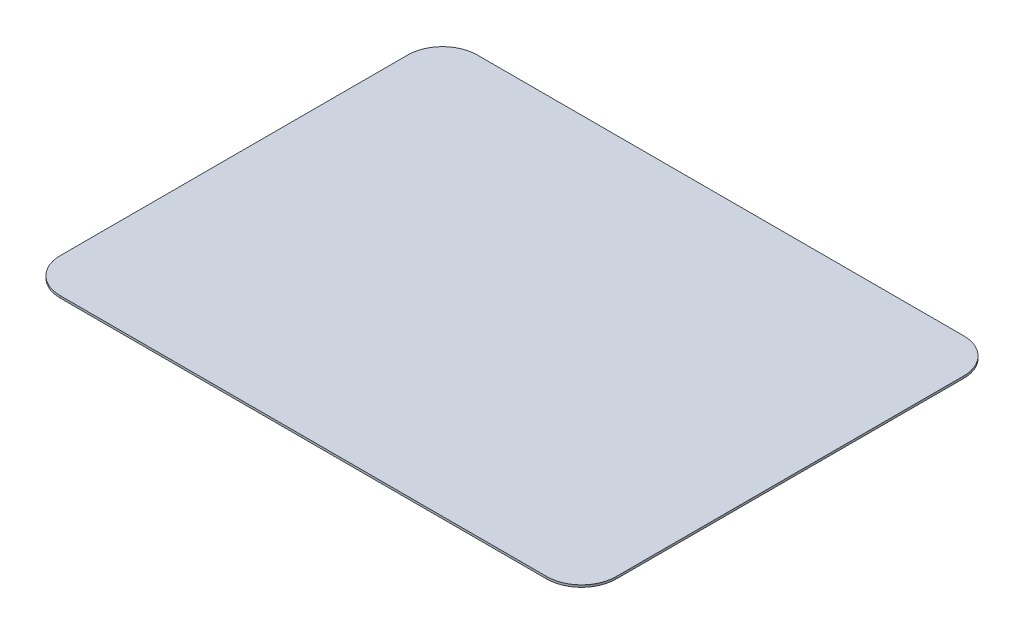
SolidWorks part; units mm, degrees
ref_plane "Front Plane" through (0, 0, 0) normal (0, 0, 1) x (1, 0, 0)
ref_plane "Top Plane" through (0, 0, 0) normal (0, 1, 0) x (1, 0, 0)
ref_plane "Right Plane" through (0, 0, 0) normal (1, 0, 0) x (0, 0, -1)
ref_plane "SheetPlane" through (0, 6.731, 0) normal (0, 1, 0) x (1, 0, 0)
sketch "Sketch1" plane through (0, 6.731, 0) normal (0, 1, 0) x (1, 0, 0)
  line L4 (101.6, -63.5) -> (101.6, 63.5)
  line L5 (88.9, 76.2) -> (-88.9, 76.2)
  line L6 (-101.6, 63.5) -> (-101.6, -63.5)
  line L7 (-88.9, -76.2) -> (88.9, -76.2)
  line L8 (101.6, -63.5) -> (101.6, 63.5)
  line L9 (88.9, 76.2) -> (-88.9, 76.2)
  line L10 (-101.6, 63.5) -> (-101.6, -63.5)
  line L11 (-88.9, -76.2) -> (88.9, -76.2)
  arc A4 (88.9, -76.2) -> (101.6, -63.5) centre (88.9, -63.5) ccw
  arc A5 (101.6, 63.5) -> (88.9, 76.2) centre (88.9, 63.5) ccw
  arc A6 (-88.9, 76.2) -> (-101.6, 63.5) centre (-88.9, 63.5) ccw
  arc A7 (-101.6, -63.5) -> (-88.9, -76.2) centre (-88.9, -63.5) ccw
  arc A8 (88.9, -76.2) -> (101.6, -63.5) centre (88.9, -63.5) ccw
  arc A9 (101.6, 63.5) -> (88.9, 76.2) centre (88.9, 63.5) ccw
  arc A10 (-88.9, 76.2) -> (-101.6, 63.5) centre (-88.9, 63.5) ccw
  arc A11 (-101.6, -63.5) -> (-88.9, -76.2) centre (-88.9, -63.5) ccw
  dimension "D1" = 0
extrude "MainBody" add sketch "Sketch1" along normal blind 0.7937
equation "\"SheetThickness\"= 0.03125in"
equation "\"D1@MainBody\" = \"SheetThickness\""
equation "\"SheetTolerance\"= 0.012in"
